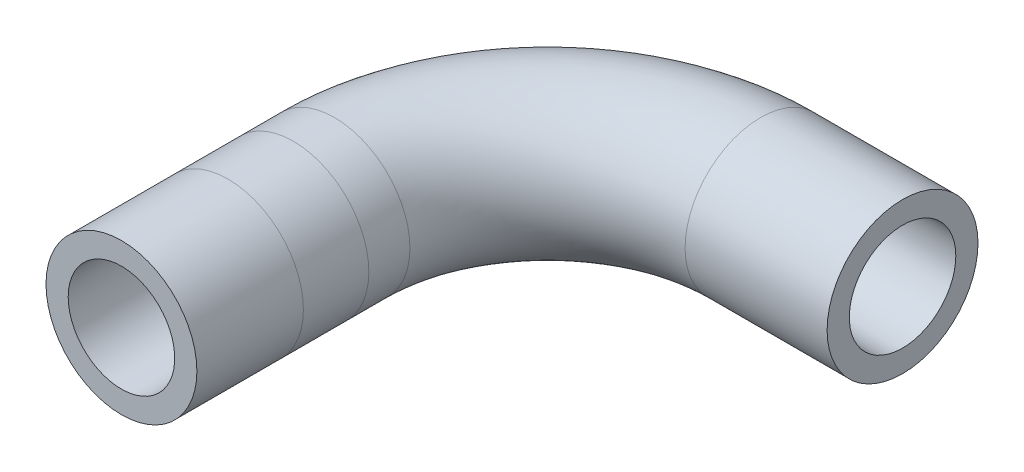
SolidWorks part; units mm, degrees
material "Silicon Rubber"
ref_plane "X-Y Datum" through (0, 0, 0) normal (0, 0, 1) x (1, 0, 0)
ref_plane "X-Z Datum" through (0, 0, 0) normal (0, 1, 0) x (1, 0, 0)
ref_plane "Y-Z Datum" through (0, 0, 0) normal (1, 0, 0) x (0, 0, -1)
sketch3d "3DSketch1"
  line L0 (-39.4506, 0, -7.35) -> (-39.4506, 0, 0)
  line L1 (-39.4506, 0, 0) -> (-39.4506, 0, 11.7)
  line L2 (-39.4506, 0, 30.75) -> (-39.4506, 0, 11.7)
  line L3 (-1.3506, 0, -45.45) -> (24.0494, 0, -45.45)
  arc A1 (-39.4506, 0, -7.35) -> (-1.3506, 0, -45.45) centre (-1.3506, 0, -7.35) cw
  circle A3 centre (-39.4506, 0, 11.7) radius 5 construction
  point P3 (-1.3506, -38.1, -7.35)
  point P7 (-39.4506, 0, 16.7)
  dimension "D2" = 38.1
  dimension "D5" = 10
  dimension "D1" = 38.1
  dimension "D3" = 90
  dimension "D4" = 25.4
  dimension "D6" = 19.05
sweep "Sweep1" add path "3DSketch1" circular profile diameter 26.9875 parameters "D3"=26.9875
sweep "Cut-Sweep1" cut path "3DSketch1<2>" circular profile diameter 19.05 parameters "D3"=19.05
sketch3d "3DSketch1<2>" same geometry as "3DSketch1"
sketch3d "3DSketch2"
  circle A0 centre (-39.4506, 0, 11.7) radius 9.525 construction
  circle A1 centre (-39.4506, 0, 11.7) radius 13.4937 construction
  circle A2 centre (-39.4506, 0, 30.75) radius 9.525 construction
  point P2 (-39.4506, 0, 21.225)
  point P5 (-39.4506, 0, -1.7937)
  point P8 (-39.4506, 0, 40.275)
